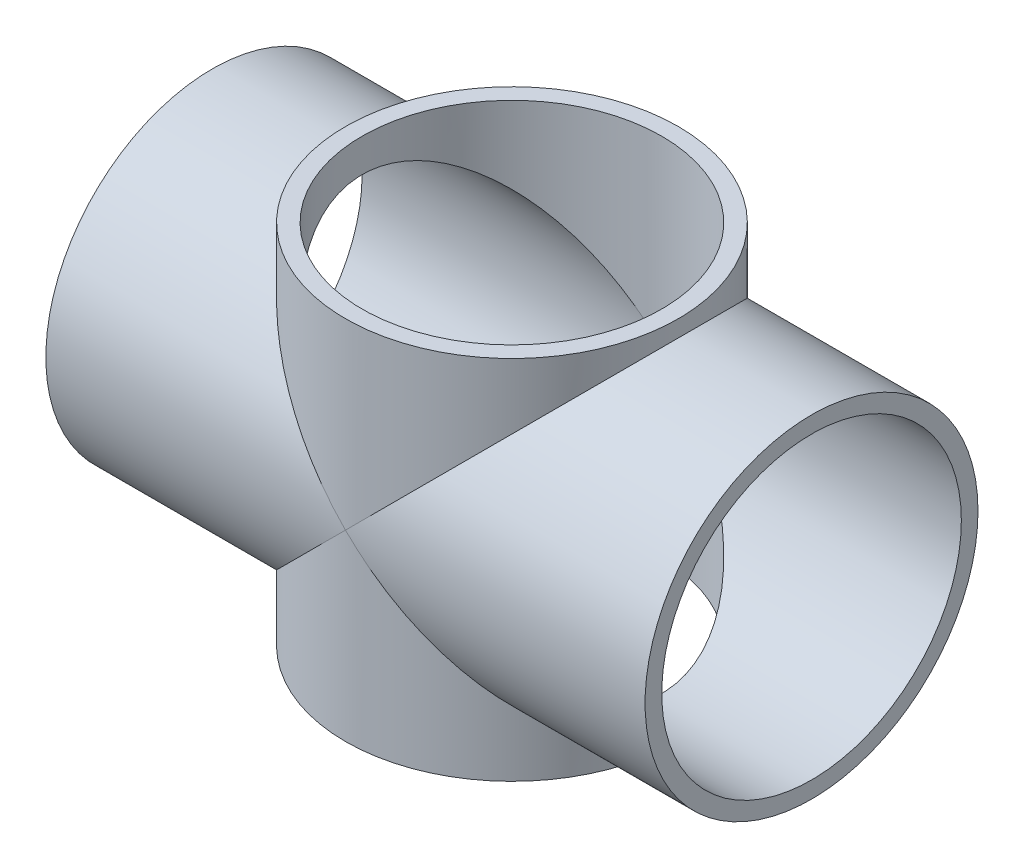
SolidWorks part; units mm, degrees
material "PVC Rigid"
ref_plane "Front Plane" through (0, 0, 0) normal (0, 0, 1) x (1, 0, 0)
ref_plane "Top Plane" through (0, 0, 0) normal (0, 1, 0) x (1, 0, 0)
ref_plane "Right Plane" through (0, 0, 0) normal (1, 0, 0) x (0, 0, -1)
sketch "Sketch2" plane through (0, 0, 0) normal (0, 1, 0) x (1, 0, 0)
  circle A0 centre (0, 0) radius 57.15
  circle A1 centre (0, 0) radius 63.5
  dimension "D1" = 114.3
  dimension "D2" = 127
extrude "Boss-Extrude1" add sketch "Sketch2" along normal blind 228.6
sketch "Sketch3" plane through (0, 0, 0) normal (1, 0, 0) x (0, 0, -1)
  circle A0 centre (0, 114.3) radius 57.15
  circle A1 centre (0, 114.3) radius 63.5
  dimension "D1" = 114.3
  dimension "D2" = 127
  dimension "D3" = 114.3
extrude "Boss-Extrude2" add sketch "Sketch3" along normal blind 114.3 and the other way blind 114.3
sketch "Sketch4" plane through (-114.3, 0, 0) normal (-1, 0, 0) x (0, 0, 1)
  circle A0 centre (0, 114.3) radius 57.15
  dimension "D1" = 114.3
extrude "Cut-Extrude1" cut sketch "Sketch4" against normal through all
sketch "Sketch5" plane through (0, 228.6, 0) normal (0, 1, 0) x (1, 0, 0)
  circle A0 centre (0, 0) radius 57.15
  dimension "D1" = 114.3
extrude "Cut-Extrude2" cut sketch "Sketch5" against normal through all
sketch "Sketch6" plane through (0, 0, 0) normal (1, 0, 0) x (0, 0, -1)
  line L0 (63.5, 228.6) -> (-63.5, 228.6) construction
  line L1 (-83.8471, 239.2421) -> (104.0632, 239.2421)
  line L2 (-83.8471, 239.2421) -> (-83.8471, 184.15)
  line L3 (-83.8471, 184.15) -> (104.0632, 184.15)
  line L4 (104.0632, 239.2421) -> (104.0632, 184.15)
  line L5 (-83.8471, 44.45) -> (96.1093, 44.45)
  line L6 (-83.8471, 44.45) -> (-83.8471, -7.6594)
  line L7 (-83.8471, -7.6594) -> (96.1093, -7.6594)
  line L8 (96.1093, 44.45) -> (96.1093, -7.6594)
  line L9 (-63.5, 0) -> (63.5, 0) construction
  dimension "D1" = 44.45
  dimension "D2" = 44.45
extrude "Cut-Extrude3" cut sketch "Sketch6" against normal through all both and the other way through all
